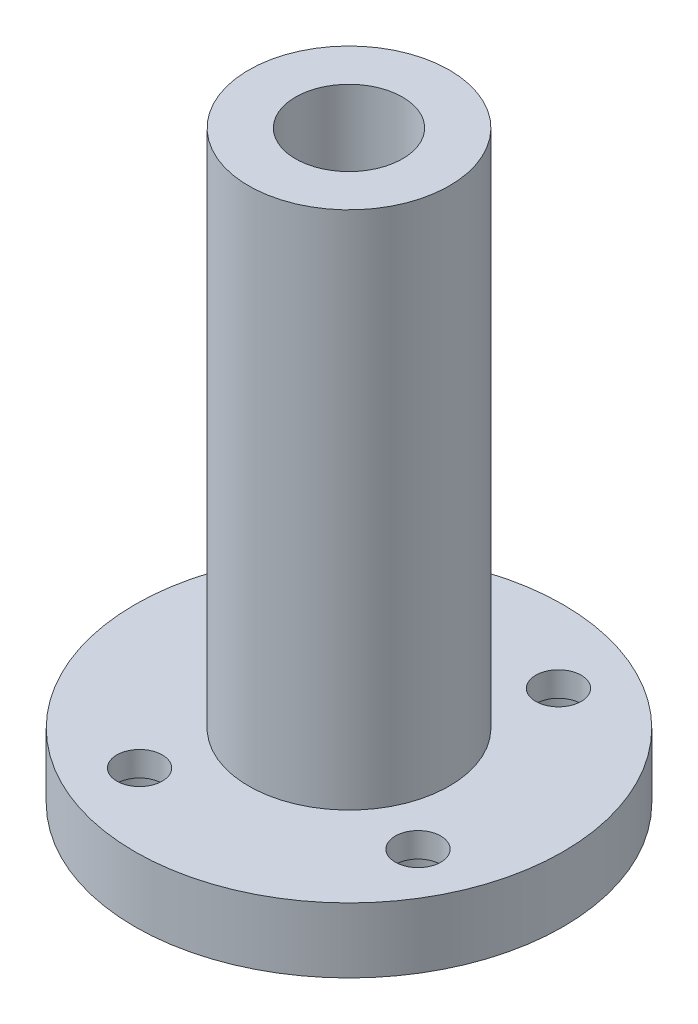
SolidWorks part; units mm, degrees
ref_plane "前视基准面" through (0, 0, 0) normal (0, 0, 1) x (1, 0, 0)
ref_plane "上视基准面" through (0, 0, 0) normal (0, 1, 0) x (1, 0, 0)
ref_plane "右视基准面" through (0, 0, 0) normal (1, 0, 0) x (0, 0, -1)
sketch "草图1" plane through (0, 0, 0) normal (0, 1, 0) x (1, 0, 0)
  circle A0 centre (0, 0) radius 4.1186
  circle A1 centre (0, 0) radius 7.7223
  circle A2 centre (0, 0) radius 16.4743
  circle A3 centre (-5.4029, -10.7149) radius 1.75
  circle A4 centre (-10.7149, 5.4029) radius 1.75
  circle A5 centre (5.4029, 10.7149) radius 1.75
  circle A6 centre (10.7149, -5.4029) radius 1.75
  point P5 (-5.4029, -10.7149)
  point P17 (0, 0)
  dimension "D1" = 12
  dimension "D2" = 4
extrude "凸台-拉伸1" add sketch "草图1" along normal blind 5 contours A2 A6 A5 A4 A3 A1 region at (-16.0083, 0, 0)
extrude "凸台-拉伸2" add sketch "草图1<3>" along normal blind 45 contours A1 A0 region at (-7.5039, 0, 0)
sketch "草图1<3>" plane through (0, 0, 0) normal (0, 1, 0) x (1, 0, 0) same geometry as "草图1"
sketch "草图2" plane through (0, 0, 0) normal (0, -1, 0) x (1, 0, 0)
  circle A0 centre (5.4029, -10.7149) radius 3
  circle A1 centre (-10.7149, -5.4029) radius 3
  circle A2 centre (-5.4029, 10.7149) radius 3
  circle A3 centre (10.7149, 5.4029) radius 3
  point P12 (0, 0)
  dimension "D1" = 4
extrude "切除-拉伸1" cut sketch "草图2" against normal blind 3.1
